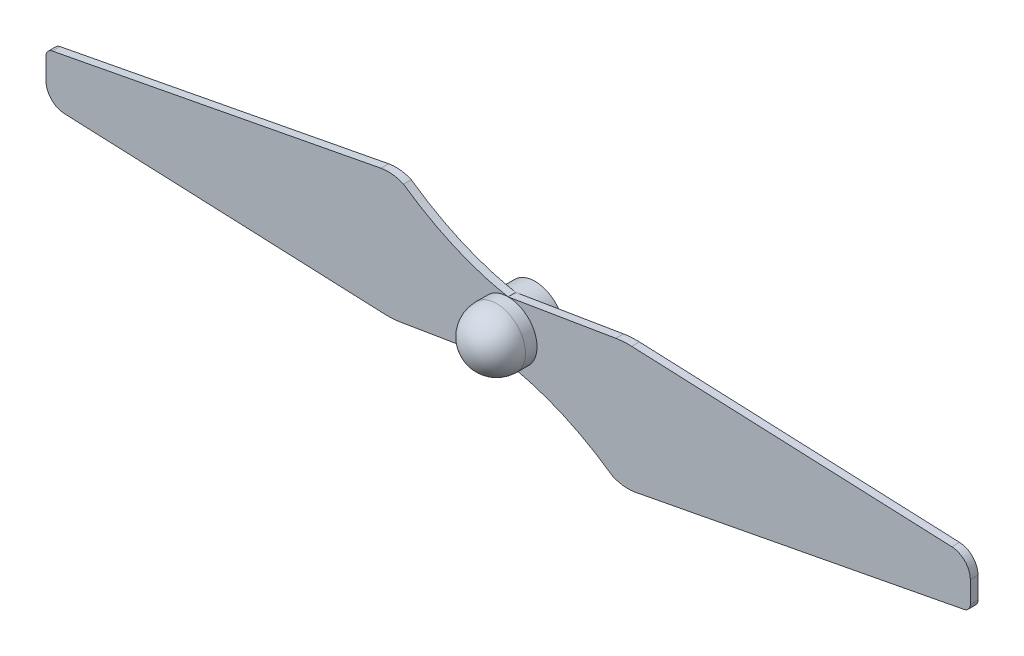
SolidWorks part; units mm, degrees
ref_plane "정면" through (0, 0, 0) normal (0, 0, 1) x (1, 0, 0)
ref_plane "윗면" through (0, 0, 0) normal (0, 1, 0) x (1, 0, 0)
ref_plane "우측면" through (0, 0, 0) normal (1, 0, 0) x (0, 0, -1)
sketch "스케치1" plane through (0, 0, 0) normal (0, 0, 1) x (1, 0, 0)
  circle A0 centre (0, 0) radius 7.5
  dimension "D1" = 15
extrude "보스-돌출1" add sketch "스케치1" along normal blind 10
ref_axis "기준축1" through (0, 0, 10) along (0, 0, -1)
ref_plane "평면2" through (0, 0, 10) normal (0, 0, 1) x (1, 0, 0)
sketch "스케치3" plane through (0, 0, 10) normal (0, 0, 1) x (1, 0, 0)
  line L0 (0, 0) -> (0, -8.1689) construction
ref_plane "평면3" through (0, 0, 0) normal (-1, 0, 0) x (0, -1, 0)
sketch "스케치4" plane through (0, 0, 0) normal (-1, 0, 0) x (0, -1, 0)
  line L0 (-7.5, 10) -> (7.5, 10)
  arc A0 (7.5, 10) -> (-7.5, 10) centre (0, 10) ccw
revolve "회전4" add sketch "스케치4" angle 360 about L0 region at (0, 0, 13.1831)
sketch "스케치5" plane through (0, 0, 0) normal (0, 0, -1) x (-1, 0, 0)
  circle A0 centre (0, 0) radius 2.5
  dimension "D1" = 5
extrude "컷-돌출1" cut sketch "스케치5" against normal blind 14
ref_plane "평면4" through (0, 0, 5) normal (0, 0, -1) x (-1, 0, 0)
sketch "스케치7" plane through (0, 0, 5) normal (0, 0, -1) x (-1, 0, 0)
  line L0 (0, 22.5) -> (0, -22.5) construction
  line L2 (120, -1.6382) -> (120, 3.9142)
  line L7 (120, -1.6382) -> (120, 3.9142)
  line L14 (-120, 1.6382) -> (-120, -3.9142)
  line L17 (0, -22.5) -> (0, 22.5) construction
  line L20 (0, -7.5) -> (0, 7.5) construction
  line L22 (-27.1726, -19.2748) -> (-14.0344, -10.0811) construction
  line L23 (-14.0344, -10.0811) -> (0, -7.5) construction
  line L24 (27.1726, 19.2748) -> (14.0344, 10.0811) construction
  line L25 (14.0344, 10.0811) -> (0, 7.5) construction
  line L26 (-27.9483, 12.158) -> (0, 7.5)
  line L27 (-115.2105, 8.9098) -> (-32.0782, 12.4124)
  line L28 (-120, -1.6382) -> (-120, 3.9142)
  line L29 (-33.0266, -19.9213) -> (-118.3756, -3.6026)
  line L30 (-120, -1.6382) -> (-120, 3.9142)
  line L31 (27.9483, -12.158) -> (0, -7.5)
  line L32 (115.2105, -8.9098) -> (32.0782, -12.4124)
  line L33 (120, 1.6382) -> (120, -3.9142)
  line L34 (33.0266, 19.9213) -> (118.3756, 3.6026)
  line L35 (120, 1.6382) -> (120, -3.9142)
  line L36 (-120, 1.6382) -> (-120, -3.9142) [skipped]
  circle A0 centre (0, 0) radius 7.5 construction
  arc A1 (27.1726, -19.2748) -> (33.0266, -19.9213) centre (31.1487, -10.0992) ccw
  arc A4 (118.3756, -3.6026) -> (120, -1.6382) centre (118, -1.6382) ccw
  arc A8 (-118.3756, 3.6026) -> (-120, 1.6382) centre (-118, 1.6382) ccw
  arc A9 (-118.3756, -3.6026) -> (-120, -1.6382) centre (-118, -1.6382) cw
  arc A10 (-120, 3.9142) -> (-115.2105, 8.9098) centre (-115, 3.9142) cw
  arc A11 (-32.0782, 12.4124) -> (-27.9483, 12.158) centre (-31.2363, -7.5698) cw
  arc A12 (-27.1726, -19.2748) -> (-33.0266, -19.9213) centre (-31.1487, -10.0992) cw
  arc A13 (118.3756, 3.6026) -> (120, 1.6382) centre (118, 1.6382) cw
  arc A14 (120, -3.9142) -> (115.2105, -8.9098) centre (115, -3.9142) cw
  arc A15 (32.0782, -12.4124) -> (27.9483, -12.158) centre (31.2363, 7.5698) cw
  arc A16 (27.1726, 19.2748) -> (33.0266, 19.9213) centre (31.1487, 10.0992) cw
  arc A17 (-27.1726, 19.2748) -> (-33.0266, 19.9213) centre (-31.1487, 10.0992) ccw [skipped]
  spline S2 degree 2 poles (-27.1726, -19.2748) (-14.0344, -10.0811) (0, -7.5) knots 0 0 0 1 1 1
  spline S3 degree 2 poles (27.1726, 19.2748) (14.0344, 10.0811) (0, 7.5) knots 0 0 0 1 1 1
  point P18 (30, -20.5)
  point P19 (-30, 20.5)
  point P21 (30, 12.5)
  point P24 (120, 8.708)
  point P27 (120, -3.292)
  point P70 (-30, -20.5)
  point P71 (120, 3.292)
  point P72 (120, -8.708)
  point P73 (30, -12.5)
  point P74 (30, 20.5)
  dimension "D8" = 10
  dimension "D11" = 2
  dimension "D2" = 2
  dimension "D3" = 12
  dimension "D4" = 30
  dimension "D5" = 5
  dimension "D6" = 30
  dimension "D7" = 13
extrude "보스-돌출2" add sketch "스케치7" against normal blind 2 contours A8 A1 A4 L2 region at (0, 0, 5)
sketch "스케치8" plane through (0, 0, 0) normal (0, 0, -1) x (-1, 0, 0)
  circle A0 centre (0, 0) radius 2.5
extrude "컷-돌출2" cut sketch "스케치8" against normal blind 12
